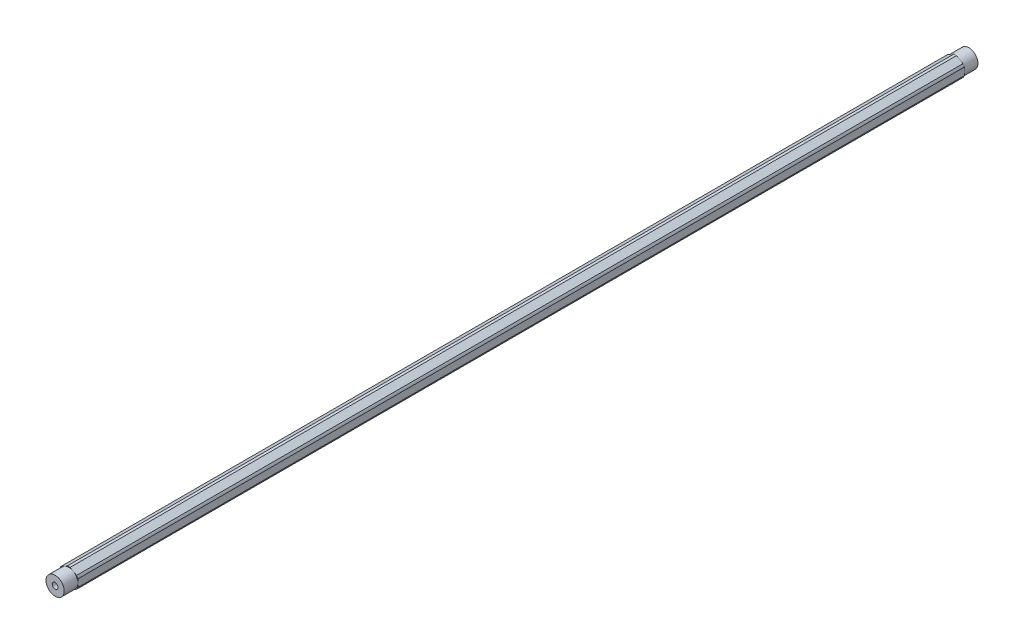
SolidWorks part; units mm, degrees
material "7075-T6 (SN)"
ref_plane "Front Plane" through (0, 0, 0) normal (0, 0, 1) x (1, 0, 0)
ref_plane "Top Plane" through (0, 0, 0) normal (0, 1, 0) x (1, 0, 0)
ref_plane "Right Plane" through (0, 0, 0) normal (1, 0, 0) x (0, 0, -1)
sketch "Sketch2" plane through (0, 0, 0) normal (0, 0, 1) x (1, 0, 0)
  line L1 (0, 7.3323) -> (-6.35, 3.6662)
  line L2 (-6.35, 3.6662) -> (-6.35, -3.6662)
  line L3 (-6.35, -3.6662) -> (0, -7.3323)
  line L4 (0, -7.3323) -> (6.35, -3.6662)
  line L5 (6.35, -3.6662) -> (6.35, 3.6662)
  line L6 (6.35, 3.6662) -> (0, 7.3323)
  circle A0 centre (0, 0) radius 6.35 construction
  circle A2 centre (0, 0) radius 2.0193
  circle A3 centre (0, 0) radius 6.858
  dimension "D1" = 12.7
  dimension "D2" = 13.716
  dimension "D3" = 4.0386
extrude "Boss-Extrude1" add sketch "Sketch2" along normal mid plane 617.0346 contours L5 A3 L6 L1 L2 L3 L4 A2 region at (0, 6.6711, 0)
sketch "Sketch7" plane through (0, 0, 308.5173) normal (0, 0, 1) x (1, 0, 0)
  circle A0 centre (0, 0) radius 6.35
  dimension "D1" = 12.7
extrude "Boss-Extrude2" add sketch "Sketch7" along normal blind 9.525
mirror "Mirror1" about plane through (0, 0, 0) normal (0, 0, 1) of "Boss-Extrude2"
hole_wizard "#10-32 Tapped Hole2" positions "3DSketch1" profile "Sketch6" tap size "#10-32" standard "ANSI Inch"
sketch3d "3DSketch1"
  line L0 (0, 0, 318.0423) -> (0, 0, 308.5173) construction
  line L1 (0, 0, -318.0423) -> (0, 0, -308.5173) construction
  point P14 (0, 0, 318.0423)
  point P18 (0, 0, -318.0423)
sketch "Sketch6" plane through (0, 0, 318.0423) normal (1, 0, 0) x (0, -1, 0)
  line L0 (0, 0) -> (0, 17.5608)
  line L1 (0, 17.5608) -> (2.0193, 16.3474)
  line L2 (2.0193, 16.3474) -> (2.0193, 0)
  line L5 (2.0193, 0) -> (0, 0)
  line L10 (0, 17.5608) -> (-2.0193, 16.3474) construction
  line L11 (0, -6.35) -> (0, 107.95) construction
  dimension "Tap Drill Dia." = 4.0386
  dimension "Tap Drill Depth" = 16.3474
  dimension "Drill Angle" = 118
cosmetic thread "Hole Thread1" parameters "D1"=13.97, "D2"=4.826
cosmetic thread "Hole Thread2" parameters "D1"=13.97, "D2"=4.826
